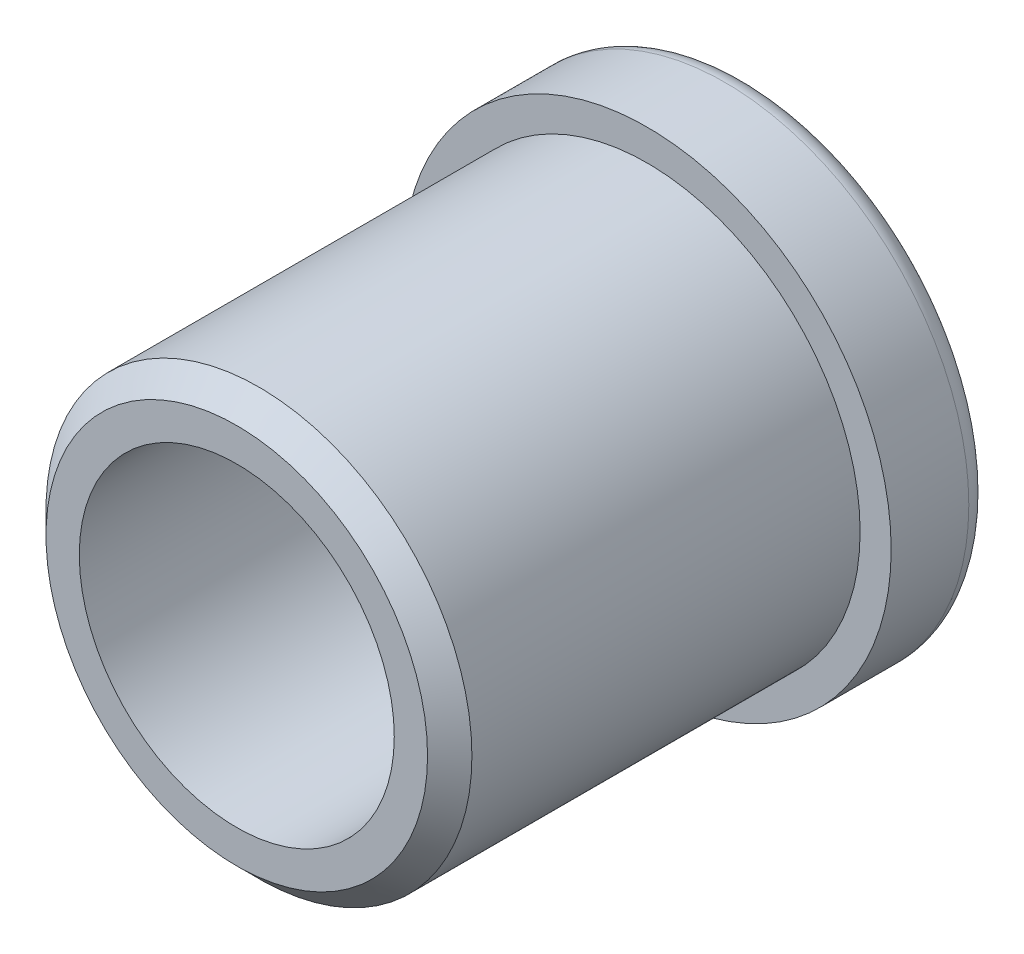
SolidWorks part; units mm, degrees
ref_plane "정면" through (0, 0, 0) normal (0, 0, 1) x (1, 0, 0)
ref_plane "윗면" through (0, 0, 0) normal (0, 1, 0) x (1, 0, 0)
ref_plane "우측면" through (0, 0, 0) normal (1, 0, 0) x (0, 0, -1)
sketch "스케치1" plane through (0, 0, 0) normal (0, 0, 1) x (1, 0, 0)
  circle A0 centre (0, 0) radius 11
  circle A1 centre (0, 0) radius 6.6
  dimension "D1" = 13.2
  dimension "D2" = 22
extrude "보스-돌출1" add sketch "스케치1" along normal blind 3
sketch "스케치2" plane through (0, 0, 3) normal (0, 0, 1) x (1, 0, 0)
  circle A0 centre (0, 0) radius 9.6
  circle A1 centre (0, 0) radius 7.1
  dimension "D1" = 19.2
  dimension "D2" = 14.2
extrude "보스-돌출2" add sketch "스케치2" along normal blind 20
chamfer "모따기1" distance 1 angle 45 1 edges at (9.6, 0, 23)
fillet "필렛1" radius 1 1 edges at (11, 0, 0)
sketch "스케치3" plane through (0, 0, 3) normal (0, 0, 1) x (1, 0, 0)
  circle A0 centre (0, 0) radius 9.6
  circle A1 centre (0, 0) radius 11
  circle A2 centre (0, 0) radius 9.6 construction
  circle A3 centre (0, 0) radius 11 construction
extrude "보스-돌출3" add sketch "스케치3" along normal blind 1.5
sketch "스케치4" plane through (0, 0, 3) normal (0, 0, 1) x (1, 0, 0)
  circle A0 centre (0, 0) radius 7.1
  circle A1 centre (0, 0) radius 6.6
  circle A2 centre (0, 0) radius 6.6 construction
  circle A3 centre (0, 0) radius 7.1 construction
extrude "보스-돌출4" add sketch "스케치4" along normal blind 8.5
sketch "스케치5" plane through (0, 0, 0) normal (0, 0, -1) x (-1, 0, 0)
  circle A0 centre (0, 0) radius 7.5
  dimension "D1" = 15
extrude "컷-돌출1" cut sketch "스케치5" against normal blind 10
chamfer "모따기2" distance 1 angle 45 2 edges at (-7.5, 0, 0) (-7.5, 0, 10)
